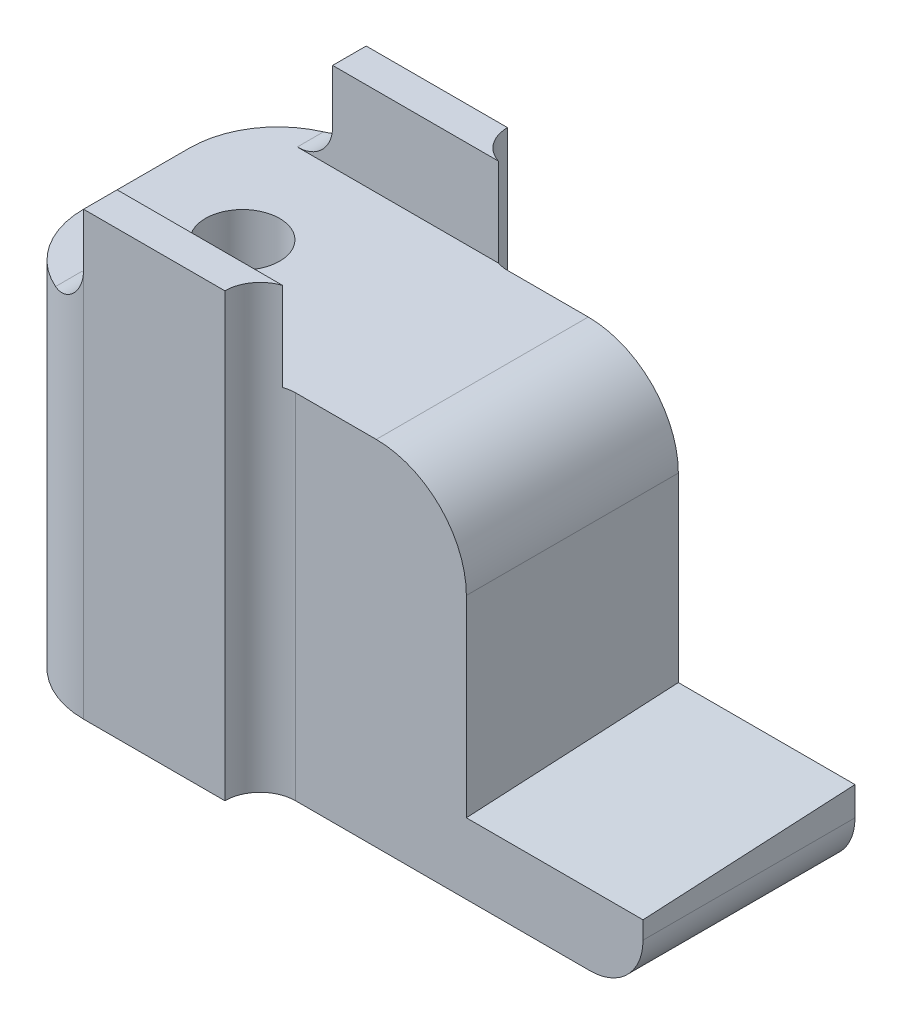
SolidWorks part; units mm, degrees
ref_plane "Front Plane" through (0, 0, 0) normal (0, 0, 1) x (1, 0, 0)
ref_plane "Top Plane" through (0, 0, 0) normal (0, 1, 0) x (1, 0, 0)
ref_plane "Right Plane" through (0, 0, 0) normal (1, 0, 0) x (0, 0, -1)
sketch "Sketch1" plane through (0, 0, 0) normal (0, 1, 0) x (1, 0, 0)
  line L5 (-6, 8) -> (6, 8)
  line L6 (-6, 8) -> (-6, -8)
  line L7 (-6, -8) -> (6, -8)
  line L8 (6, 8) -> (6, -8)
  line L9 (-6, 8) -> (6, -8) construction
  line L10 (-6, -8) -> (6, 8) construction
  line L11 (6, 8) -> (7, 8)
  line L12 (6, 8) -> (6, -8)
  line L13 (6, -8) -> (7, -8)
  line L14 (7, 8) -> (7, -8)
  circle A0 centre (0, 0) radius 2.1
  point P0 (0, 0)
  dimension "D1" = 4.2
  dimension "D2" = 16
  dimension "D3" = 6
  dimension "D4" = 1
extrude "Boss-Extrude1" add sketch "Sketch1" along normal blind 20 contours L8 L5 L6 L7 A0 | L14 L11 L8 L13 region at (0, 0, -7.8) region at (6.5, 0, 0)
fillet "Fillet1" radius 5 2 edges at (-6, 10, -8) (-6, 10, 8)
sketch "Sketch2" plane through (0, 20, 0) normal (0, 1, 0) x (1, 0, 0)
  line L0 (7, 0) -> (-6, 0) construction
  line L1 (7, 8) -> (-1, 8)
  line L2 (7, 8) -> (7, 6.1)
  line L3 (7, 6.1) -> (-1, 6.1)
  line L4 (-1, 8) -> (-1, 6.1)
  line L5 (7, 8) -> (7, -8) construction
  line L6 (-6, 3) -> (-6, -3) construction
  line L7 (-1, -8) -> (-1, -6.1)
  line L8 (7, -6.1) -> (-1, -6.1)
  line L9 (7, -8) -> (7, -6.1)
  line L10 (7, -8) -> (-1, -8)
  line L11 (-1, 8) -> (7, 8) construction
  dimension "D1" = 1.9
extrude "Boss-Extrude2" add sketch "Sketch2" along normal blind 5
sketch "Sketch4" plane through (7, 0, 0) normal (1, 0, 0) x (0, 0, -1)
  line L0 (8, 25) -> (8, 0) construction
  line L1 (-6, 0) -> (6, 0)
  line L2 (-6, 0) -> (-6, 20)
  line L3 (-6, 20) -> (6, 20)
  line L4 (6, 0) -> (6, 20)
  line L6 (6.1, 20) -> (-6.1, 20) construction
  point P6 (0, 0)
  dimension "D1" = 2
extrude "Boss-Extrude3" add sketch "Sketch4" along normal offset from surface (11.67 mm away) 24.67 up to face at (-6, 10, 0)
fillet "Fillet2" radius 5.1 1 edges at (18.67, 20, 0)
fillet "Fillet4" radius 2 2 edges at (-1, 20, -7.05) (-1, 20, 7.05)
fillet "Fillet6" radius 2 2 edges at (7, 10, -6) (7, 10, 6)
sketch "Sketch5" plane through (18.67, 0, 0) normal (1, 0, 0) x (0, 0, -1)
  line L0 (-6, 4) -> (6, 4.6289)
  line L1 (-6, 14.9) -> (-6, 0) construction
  line L2 (6, 0) -> (6, 20) construction
  line L3 (-6, 4) -> (-6, 0)
  line L4 (-6, 0) -> (6, 0)
  line L5 (6, 0) -> (6, 4.6289)
  line L6 (-6, 4) -> (6, 4) construction
  dimension "D1" = 4
  dimension "D2" = 3
extrude "Boss-Extrude4" add sketch "Sketch5" along normal blind 10
fillet "Fillet7" radius 3 1 edges at (28.67, 0, 0)
